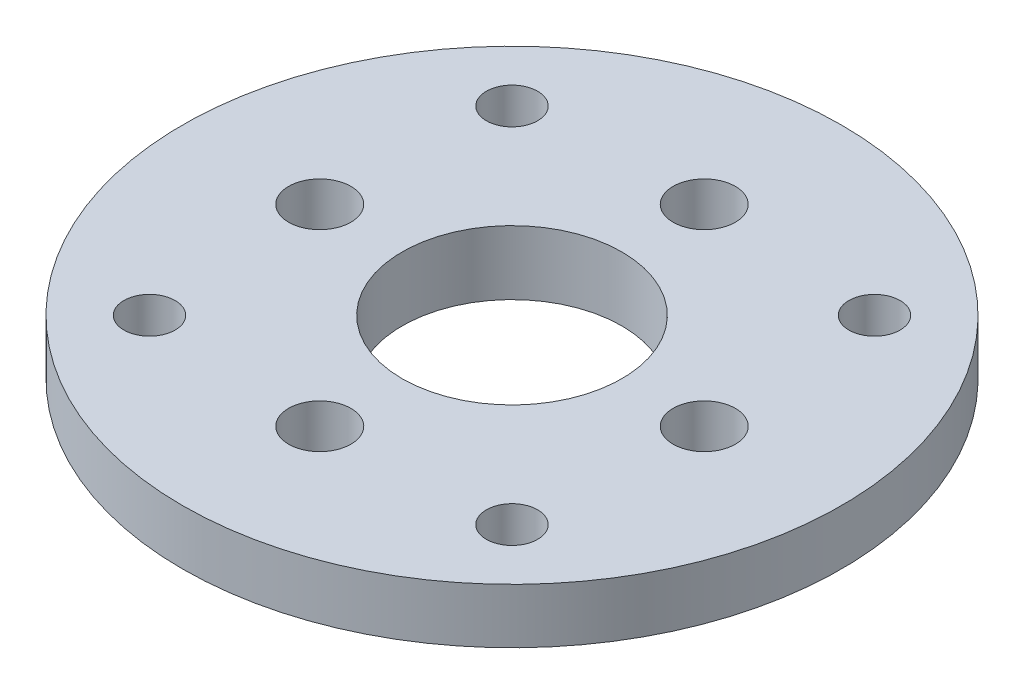
SolidWorks part; units mm, degrees
ref_plane "Front Plane" through (0, 0, 0) normal (0, 0, 1) x (1, 0, 0)
ref_plane "Top Plane" through (0, 0, 0) normal (0, 1, 0) x (1, 0, 0)
ref_plane "Right Plane" through (0, 0, 0) normal (1, 0, 0) x (0, 0, -1)
sketch "Sketch1" plane through (0, 0, 0) normal (0, 1, 0) x (1, 0, 0)
  circle A0 centre (0, 0) radius 16.5
  dimension "D1" = 33
extrude "Boss-Extrude1" add sketch "Sketch1" along normal blind 0.5
sketch "Sketch2" plane through (0, 0.5, 0) normal (0, 1, 0) x (1, 0, 0)
  circle A0 centre (0, 0) radius 18
  dimension "D1" = 36
extrude "Boss-Extrude2" add sketch "Sketch2" along normal blind 3
sketch "Sketch3" plane through (0, 0, 0) normal (0, 1, 0) x (1, 0, 0)
  circle A0 centre (0, 0) radius 6
  dimension "D1" = 12
extrude "Cut-Extrude1" cut sketch "Sketch3" along normal through all
sketch "Sketch4" plane through (0, 0, 0) normal (0, 1, 0) x (1, 0, 0)
  line L0 (-1.925, 0) -> (1.925, 0) construction
  circle A0 centre (10.5, 0) radius 1.7
  dimension "D2" = 3.4
  dimension "D1" = 10.5
extrude "Cut-Extrude2" cut sketch "Sketch4" along normal through all
pattern_circular "CirPattern1" count 4 over 360 about axis through (0, 3.5, 0) along (0, -1, 0) of "Cut-Extrude2"
sketch "Sketch5" plane through (0, 0, 0) normal (0, 1, 0) x (1, 0, 0)
  line L0 (0, 0) -> (20.333, 0) construction
  line L1 (0, 0) -> (16.7478, 16.7478) construction
  circle A0 centre (9.8995, 9.8995) radius 1.4
  dimension "D3" = 2.8
  dimension "D1" = 45
  dimension "D2" = 14
extrude "Cut-Extrude3" cut sketch "Sketch5" along normal through all
pattern_circular "CirPattern2" count 4 over 360 about axis through (0, 3.5, 0) along (0, -1, 0) of "Cut-Extrude3"
equation "\"pin_circle_R\" = 27"
equation "\"ecc\" = 1.5"
equation "\"n_pins\" = 11"
equation "\"pin_d\" = 3"
equation "\"out_pin_R\" = 18.5"
equation "\"disc_clr\" = 0.1"
equation "\"seat_6803\" = 26.1"
equation "\"disc_t\" = 5"
equation "\"out_hole_clr\" = 0.5"
equation "\"boss_17\" = 17.20"
equation "\"rotor_bolt_R\" = 10"
equation "\"m25_clr\" = 2.8"
equation "\"m25_head\" = 5"
equation "\"insert_hole\" = 4.4"
equation "\"csk\" = 0.6"
equation "\"peg_d\" = 3.0"
equation "\"plug_d\" = 8.6"
equation "\"peg_clr\" = 0.3"
equation "\"m3_clr\" = 3.4"
equation "\"m3_head\" = 6.2"
equation "\"pin_press\" = 3.2"
equation "\"hub_30\" = 30.25"
equation "\"hub_short\" = 0.2"
equation "\"m3_tap\" = 2.8"
equation "\"D2@Sketch4\"=\"m3_clr\""
equation "\"D3@Sketch5\"=\"m3_tap\""
equation "\"seat_6806\" = 42.1"
equation "\"pin_slip\" = 3.3"
equation "\"rear_plate_t\" = 2"
equation "\"motor_ring\" = 40.4"
